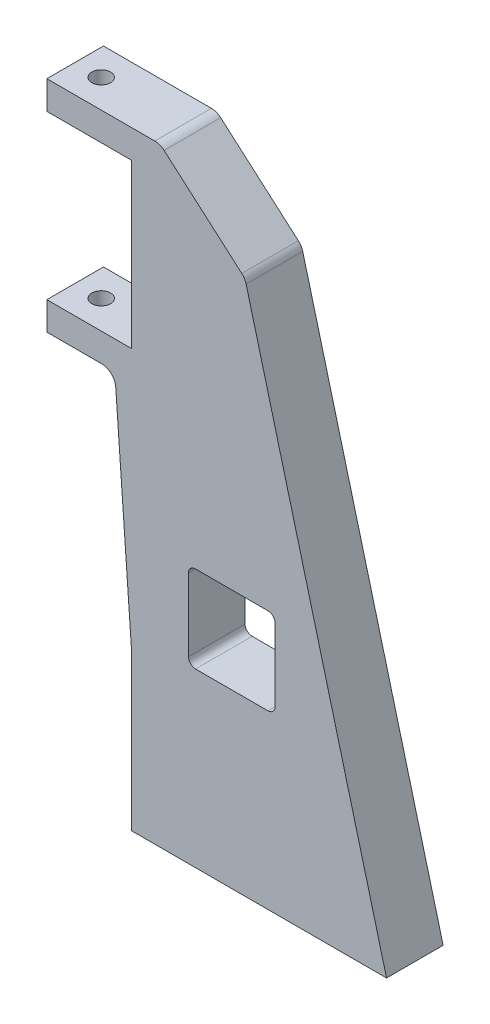
SolidWorks part; units mm, degrees
ref_plane "Front Plane" through (0, 0, 0) normal (0, 0, 1) x (1, 0, 0)
ref_plane "Top Plane" through (0, 0, 0) normal (0, 1, 0) x (1, 0, 0)
ref_plane "Right Plane" through (0, 0, 0) normal (1, 0, 0) x (0, 0, -1)
sketch "Sketch1" plane through (0, 0, 0) normal (0, 0, 1) x (1, 0, 0)
  line L0 (0, 0) -> (0, 12.7)
  line L1 (0, 12.7) -> (50.8, 12.7)
  line L2 (50.8, 12.7) -> (88.9, -20.5102)
  line L3 (0, 0) -> (38.0187, 0)
  line L4 (38.0187, 0) -> (38.0187, -73.1523)
  line L5 (38.0187, -73.1523) -> (0, -73.1523)
  line L6 (0, -73.1523) -> (0, -85.7639)
  line L7 (0, -85.7639) -> (30.48, -85.7639)
  line L10 (38.0187, -260.5159) -> (152.4, -260.5159)
  line L11 (152.4, -260.5159) -> (88.9, -20.5102)
  line L15 (30.48, -85.7639) -> (38.0187, -190.6965)
  line L16 (38.0187, -190.6965) -> (38.0187, -260.5159)
  dimension "D1" = 50.8
  dimension "D2" = 12.7
  dimension "D3" = 38.0187
  dimension "D4" = 73.1523
  dimension "D5" = 152.4
  dimension "D6" = 38.1
  dimension "D7" = 30.48
  dimension "D9" = 12.6117
  dimension "D10" = 174.752
extrude "Boss-Extrude1" add sketch "Sketch1" along normal blind 25.4
sketch "Sketch2" plane through (0, 0, 0) normal (0, 0, -1) x (-1, 0, 0)
  line L0 (0, -85.7639) -> (-30.48, -85.7639) construction
  line L1 (-63.5246, -183.2999) -> (-102.3866, -183.2999)
  line L2 (-63.5246, -183.2999) -> (-63.5246, -144.4379)
  line L3 (-63.5246, -144.4379) -> (-102.3866, -144.4379)
  line L4 (-102.3866, -183.2999) -> (-102.3866, -144.4379)
  line L5 (-38.0187, -190.6965) -> (-38.0187, -260.5159) construction
  dimension "D1" = 38.862
  dimension "D2" = 38.862
  dimension "D3" = 58.674
  dimension "D4" = 25.5059
extrude "Cut-Extrude1" cut sketch "Sketch2" against normal through all
fillet "Fillet1" radius 6.35 4 edges at (38.0187, -190.6965, 12.7) (30.48, -85.7639, 12.7) (88.9, -20.5102, 12.7) (50.8, 12.7, 12.7)
fillet "Fillet2" radius 3.175 4 edges at (63.5246, -183.2999, 12.7) (102.3866, -183.2999, 12.7) (102.3866, -144.4379, 12.7) (63.5246, -144.4379, 12.7)
sketch "Sketch3" plane through (0, 12.7, 0) normal (0, 1, 0) x (1, 0, 0)
  line L0 (48.4209, 0) -> (0, 0) construction
  line L1 (0, -25.4) -> (0, 0) construction
  circle A0 centre (11.684, -12.7) radius 4.191
  dimension "D3" = 8.382
  dimension "D1" = 12.7
  dimension "D2" = 11.684
extrude "Cut-Extrude2" cut sketch "Sketch3" against normal through all
sketch "Sketch4" plane through (0, -260.5159, 0) normal (0, -1, 0) x (1, 0, 0)
  line L0 (152.4, 25.4) -> (152.4, 0) construction
  line L1 (38.0187, 25.4) -> (152.4, 25.4) construction
  circle A0 centre (139.7, 12.7) radius 4.191
  circle A1 centre (63.5, 12.7) radius 4.191
  dimension "D1" = 8.382
  dimension "D2" = 8.382
  dimension "D3" = 12.7
  dimension "D4" = 12.7
  dimension "D5" = 76.2
  dimension "D6" = 12.7
extrude "Cut-Extrude3" cut sketch "Sketch4" against normal blind 25.4
